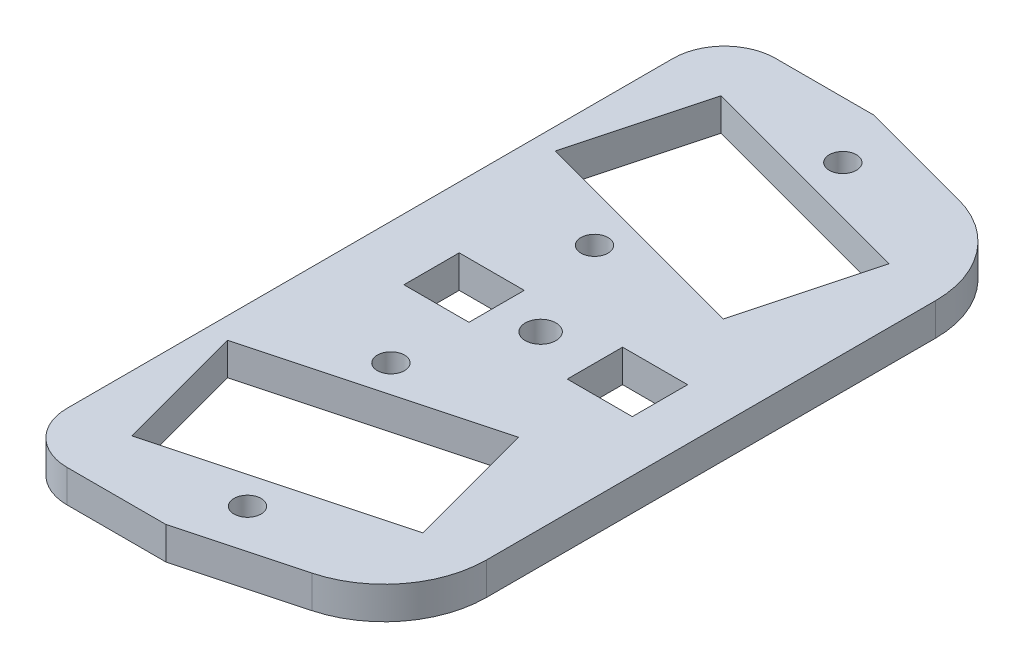
SolidWorks part; units mm, degrees
ref_plane "Front Plane" through (0, 0, 0) normal (0, 0, 1) x (1, 0, 0)
ref_plane "Top Plane" through (0, 0, 0) normal (0, 1, 0) x (1, 0, 0)
ref_plane "Right Plane" through (0, 0, 0) normal (1, 0, 0) x (0, 0, -1)
sketch "Sketch1" plane through (0, 0, 0) normal (0, 1, 0) x (1, 0, 0)
  line L0 (239.3314, 11.1978) -> (261.7408, 5.1932)
  line L1 (242.2575, 29.7812) -> (251.8972, 29.7812)
  line L2 (237.2575, 24.7812) -> (237.2575, -34.3947)
  line L4 (270.5575, 17.1079) -> (270.5575, -26.7215)
  line L5 (239.3314, 11.1978) -> (242.7484, 23.9504)
  line L6 (261.7408, 5.1932) -> (265.1579, 17.9458)
  line L7 (242.7484, 23.9504) -> (265.1579, 17.9458)
  line L8 (253.0712, 24.5996) -> (255.6305, 23.9137) construction
  line L9 (252.1737, 16.1327) -> (251.4878, 13.5732) construction
  line L10 (241.0399, 17.5741) -> (263.4494, 11.5695) construction
  line L11 (237.2575, -4.8068) -> (270.5575, -4.8068) construction
  line L12 (241.0399, -27.1877) -> (263.4494, -21.1831) construction
  line L13 (252.1737, -25.7463) -> (251.4878, -23.1868) construction
  line L14 (253.0712, -34.2132) -> (255.6305, -33.5273) construction
  line L15 (261.7408, -14.8068) -> (265.1579, -27.5593)
  line L16 (239.3314, -20.8114) -> (261.7408, -14.8068)
  line L17 (242.7484, -33.5639) -> (239.3314, -20.8114)
  line L18 (265.1579, -27.5593) -> (242.7484, -33.5639)
  line L19 (251.8972, -39.3947) -> (263.1457, -36.3807)
  line L20 (243.2575, -7.5068) -> (249.6075, -7.5068)
  line L21 (243.2575, -7.5068) -> (243.2575, -2.1068)
  line L22 (243.2575, -2.1068) -> (249.6075, -2.1068)
  line L23 (249.6075, -7.5068) -> (249.6075, -2.1068)
  line L24 (243.2575, -7.5068) -> (249.6075, -2.1068) construction
  line L25 (243.2575, -2.1068) -> (249.6075, -7.5068) construction
  line L26 (259.2075, -7.5068) -> (265.5575, -7.5068)
  line L27 (259.2075, -7.5068) -> (259.2075, -2.1068)
  line L28 (259.2075, -2.1068) -> (265.5575, -2.1068)
  line L29 (265.5575, -7.5068) -> (265.5575, -2.1068)
  line L30 (259.2075, -7.5068) -> (265.5575, -2.1068) construction
  line L31 (259.2075, -2.1068) -> (265.5575, -7.5068) construction
  line L32 (251.8972, 29.7812) -> (263.1457, 26.7672)
  line L33 (242.2575, -39.3947) -> (251.8972, -39.3947)
  circle A0 centre (254.3509, 24.2567) radius 1.3248
  circle A1 centre (249.2262, 5.1313) radius 1.3248
  circle A2 centre (249.2262, -14.7449) radius 1.3248
  circle A3 centre (254.3509, -33.8702) radius 1.3248
  circle A4 centre (253.9075, -4.8068) radius 1.5
  arc A5 (237.2575, -34.3947) -> (242.2575, -39.3947) centre (242.2575, -34.3947) ccw
  arc A6 (270.5575, -26.7215) -> (263.1457, -36.3807) centre (260.5575, -26.7215) cw
  arc A7 (270.5575, 17.1079) -> (263.1457, 26.7672) centre (260.5575, 17.1079) ccw
  arc A8 (242.2575, 29.7812) -> (237.2575, 24.7812) centre (242.2575, 24.7812) ccw
  point P26 (246.4325, -4.8068)
  point P31 (262.3825, -4.8068)
  point P43 (270.5575, -34.3947)
  point P44 (270.5575, 29.7812)
  point P47 (237.2575, 29.7812)
  point P51 (270.5575, 24.7812)
  dimension "D10" = 3
  dimension "D11" = 5
  dimension "D12" = 19.8
  dimension "D9" = 10
  dimension "D1" = 10
  dimension "D2" = 5.4
  dimension "D3" = 5.4
  dimension "D4" = 6.35
  dimension "D5" = 6.35
  dimension "D6" = 5
  dimension "D7" = 9.6
  dimension "D8" = 6
  dimension "D13" = 8
  dimension "D14" = 23.2
  dimension "D15" = 13.2024
extrude "Boss-Extrude1" add sketch "Sketch1" along normal blind 3.175
